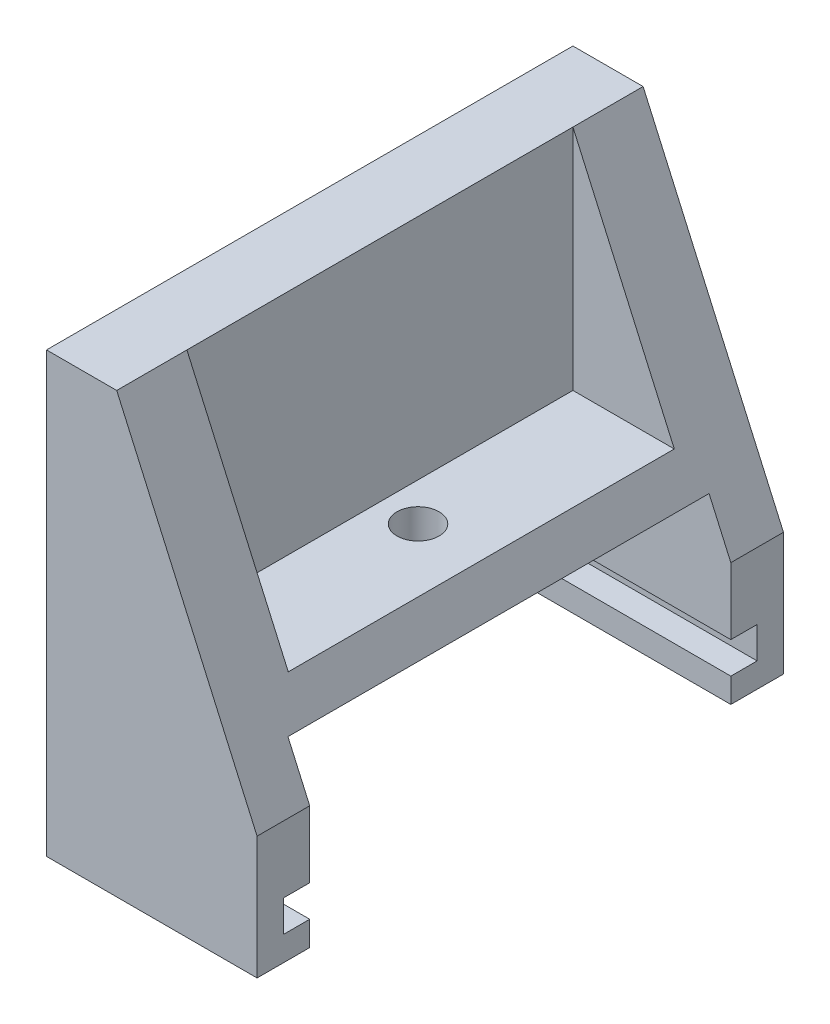
SolidWorks part; units mm, degrees
ref_plane "Front Plane" through (0, 0, 0) normal (0, 0, 1) x (1, 0, 0)
ref_plane "Top Plane" through (0, 0, 0) normal (0, 1, 0) x (1, 0, 0)
ref_plane "Right Plane" through (0, 0, 0) normal (1, 0, 0) x (0, 0, -1)
sketch "Sketch1" plane through (0, 0, 0) normal (0, 0, 1) x (1, 0, 0)
  line L0 (0, 0) -> (0, -25)
  line L1 (0, -25) -> (12, -25)
  line L2 (12, -25) -> (12, -18)
  line L3 (12, -18) -> (4, 0)
  line L4 (4, 0) -> (0, 0)
  dimension "D1" = 25
  dimension "D2" = 12
  dimension "D3" = 7
  dimension "D4" = 4
extrude "Boss-Extrude1" add sketch "Sketch1" against normal blind 30
sketch "Sketch4" plane through (0, 0, 0) normal (-1, 0, 0) x (0, 0, 1)
  line L0 (-30, 0) -> (-30, -25) construction
  line L1 (-27, -15.208) -> (-3, -15.208)
  line L2 (-27, -15.208) -> (-27, -25.208)
  line L3 (-27, -25.208) -> (-3, -25.208)
  line L4 (-3, -15.208) -> (-3, -25.208)
  point P4 (-27, -20.208)
  dimension "D1" = 24
  dimension "D2" = 10
  dimension "D3" = 3
extrude "Cut-Extrude2" cut sketch "Sketch4" against normal blind 25 contours L2 L1 L4 L3
sketch "Sketch5" plane through (0, 0, 0) normal (-1, 0, 0) x (0, 0, 1)
  line L0 (-3, -15.208) -> (-3, -25) construction
  line L1 (-3, -21.8) -> (-1.5, -21.8)
  line L2 (-3, -21.8) -> (-3, -23.6)
  line L3 (-3, -23.6) -> (-1.5, -23.6)
  line L4 (-1.5, -21.8) -> (-1.5, -23.6)
  line L5 (-3, -25) -> (0, -25) construction
  dimension "D1" = 1.8
  dimension "D2" = 1.5
  dimension "D3" = 1.4
extrude "Cut-Extrude3" cut sketch "Sketch5" against normal blind 15
ref_plane "Plane1" through (0, 0, -15) normal (0, 0, 1) x (1, 0, 0)
mirror "Mirror1" about plane through (0, 0, -15) normal (0, 0, 1) of "Cut-Extrude3"
sketch "Sketch6" plane through (0, 0, -15) normal (0, 0, 1) x (1, 0, 0)
  line L0 (4, 0) -> (4, -13)
  line L1 (4, -13) -> (9.7778, -13)
  line L2 (12, -18) -> (4, 0) construction
  line L3 (9.7778, -13) -> (4, 0)
  dimension "D1" = 13
extrude "Cut-Extrude4" cut sketch "Sketch6" against normal mid plane 22
sketch "Sketch7" plane through (0, -13, 0) normal (0, 1, 0) x (1, 0, 0)
  line L0 (-6.6, 15) -> (6.6, 15) construction
  circle A0 centre (6.1728, 15) radius 1.2
  dimension "D1" = 2.4
extrude "Cut-Extrude5" cut sketch "Sketch7" against normal blind 4 contours A0
